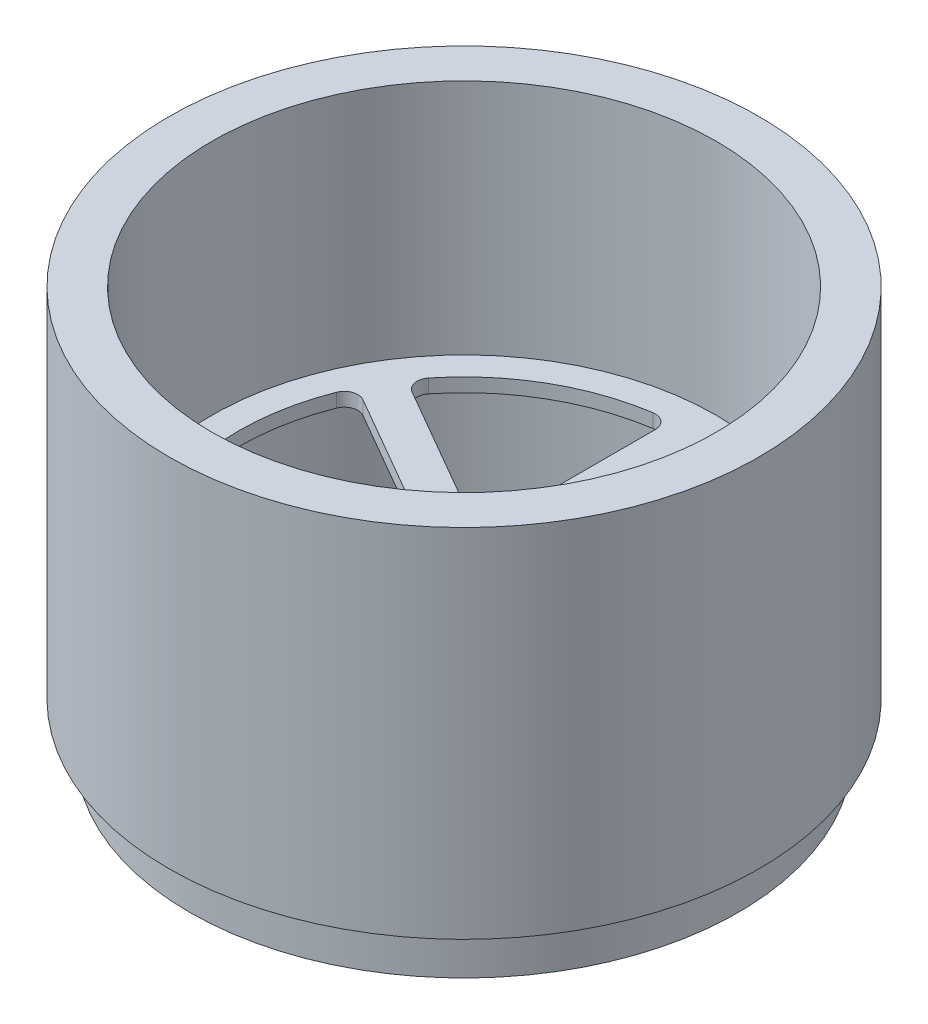
SolidWorks part; units mm, degrees
material "6061-T4 (SS)"
ref_plane "Front Plane" through (0, 0, 0) normal (0, 0, 1) x (1, 0, 0)
ref_plane "Top Plane" through (0, 0, 0) normal (0, 1, 0) x (1, 0, 0)
ref_plane "Right Plane" through (0, 0, 0) normal (1, 0, 0) x (0, 0, -1)
sketch "Sketch1" plane through (0, 0, 0) normal (0, 1, 0) x (1, 0, 0)
  circle A0 centre (0, 0) radius 21.5
  circle A1 centre (0, 0) radius 18.38
extrude "Boss-Extrude1" add sketch "Sketch1" along normal blind 29.5
ref_plane "Plane1" through (0, 11.2, 0) normal (0, -1, 0) x (-1, 0, 0)
sketch "Sketch3" plane through (0, 11.2, 0) normal (0, -1, 0) x (-1, 0, 0)
  circle A0 centre (0, 0) radius 21.5
extrude "Boss-Extrude2" add sketch "Sketch3" against normal blind 1
sketch "Sketch4" plane through (0, 11.2, 0) normal (0, -1, 0) x (-1, 0, 0)
  circle A0 centre (0, 0) radius 0.75
  circle A1 centre (0, 0) radius 2
extrude "Boss-Extrude3" add sketch "Sketch4" along normal blind 3.8
sketch "Sketch5" plane through (0, 0, 0) normal (0, 1, 0) x (1, 0, 0)
  circle A0 centre (0, 0) radius 20
extrude "Cut-Extrude1" cut sketch "Sketch5" along normal blind 3.5 flip side to cut
sketch "Sketch6" plane through (0, 11.2, 0) normal (0, -1, 0) x (-1, 0, 0)
  line L0 (1.3115, -4.359) -> (1.3115, -15.2454)
  line L1 (0, 0) -> (8.2098, -14.2199) construction
  line L2 (3.1192, -3.3153) -> (12.5472, -8.7585)
  circle A0 centre (0, 0) radius 16.4197 construction
  circle A1 centre (0, 0) radius 3.9339 construction
  arc A2 (2.4614, -16.2341) -> (12.8285, -10.2487) centre (0, 0) ccw
  arc A3 (1.843, -3.4755) -> (2.0883, -3.3339) centre (0, 0) ccw
  arc A4 (1.3115, -15.2454) -> (2.4614, -16.2341) centre (2.3115, -15.2454) ccw
  arc A5 (12.5472, -8.7585) -> (12.8285, -10.2487) centre (12.0472, -9.6246) cw
  arc A6 (3.1192, -3.3153) -> (2.0883, -3.3339) centre (2.6192, -4.1813) ccw
  arc A7 (1.3115, -4.359) -> (1.843, -3.4755) centre (2.3115, -4.359) cw
  point P13 (1.3115, -16.3672)
  point P14 (13.5187, -9.3194)
  point P17 (2.5562, -2.9902)
  point P20 (1.3115, -3.7089)
  dimension "D1" = 1
  dimension "D2" = 1
  dimension "D3" = 1
  dimension "D4" = 1
extrude "Cut-Extrude2" cut sketch "Sketch6" against normal up to next
pattern_circular "CirPattern1" count 6 over 360 about axis through (0, 7.4, 0) along (0, -1, 0) of "Cut-Extrude2"
